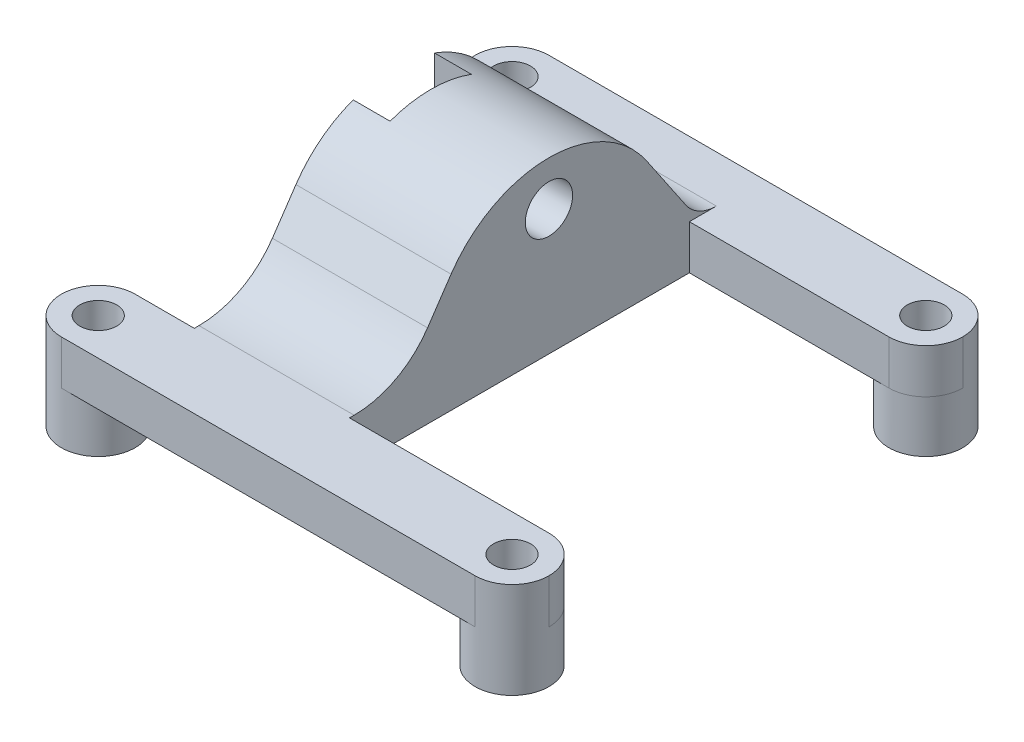
SolidWorks part; units mm, degrees
ref_plane "Plan de face" through (0, 0, 0) normal (0, 0, 1) x (1, 0, 0)
ref_plane "Plan de dessus" through (0, 0, 0) normal (0, 1, 0) x (1, 0, 0)
ref_plane "Plan de droite" through (0, 0, 0) normal (1, 0, 0) x (0, 0, -1)
sketch "Esquisse2" plane through (0, 0, 0) normal (0, 1, 0) x (1, 0, 0)
  line L0 (-16.5, 0) -> (16.5, 0) construction
  line L1 (-16.5, 16.5) -> (16.5, 16.5)
  line L2 (-16.5, 16.5) -> (-16.5, -16.5)
  line L3 (-16.5, -16.5) -> (16.5, -16.5)
  line L4 (16.5, 16.5) -> (16.5, -16.5)
  line L5 (-14, 0) -> (14, 0) construction
  line L6 (-14, 14) -> (14, 14) construction
  line L7 (-14, 14) -> (-14, -14) construction
  line L8 (-14, -14) -> (14, -14) construction
  line L9 (14, 14) -> (14, -14) construction
  circle A0 centre (-14, 14) radius 1.25
  circle A1 centre (14, 14) radius 1.25
  circle A2 centre (-14, -14) radius 1.25
  circle A3 centre (14, -14) radius 1.25
  dimension "D4" = 2.5
  dimension "D5" = 2.5
  dimension "D6" = 2.5
  dimension "D7" = 2.5
  dimension "D1" = 33
  dimension "D2" = 33
  dimension "D3" = 28
extrude "Boss.-Extru.1" add sketch "Esquisse2" along normal blind 3
fillet "Congé1" radius 2.5 4 edges at (-16.5, 1.5, -16.5) (16.5, 1.5, -16.5) (16.5, 1.5, 16.5) (-16.5, 1.5, 16.5)
sketch "Esquisse3" plane through (0, 0, 0) normal (0, -1, 0) x (1, 0, 0)
  circle A0 centre (-14, 14) radius 2.5
  arc A3 (-14, 16.5) -> (-16.5, 14) centre (-14, 14) ccw construction
  circle A4 centre (-14, 14) radius 1.25
  circle A5 centre (-14, 14) radius 1.25 construction
  circle A6 centre (14, 14) radius 2.5
  circle A7 centre (14, 14) radius 1.25
  circle A8 centre (14, 14) radius 1.25 construction
  arc A9 (16.5, 14) -> (14, 16.5) centre (14, 14) ccw construction
  circle A10 centre (14, -14) radius 2.5
  circle A11 centre (14, -14) radius 1.25
  circle A12 centre (14, -14) radius 1.25 construction
  arc A13 (14, -16.5) -> (16.5, -14) centre (14, -14) ccw construction
  circle A14 centre (-14, -14) radius 2.5
  arc A15 (-16.5, -14) -> (-14, -16.5) centre (-14, -14) ccw construction
  circle A16 centre (-14, -14) radius 1.25
  circle A17 centre (-14, -14) radius 1.25 construction
extrude "Boss.-Extru.2" add sketch "Esquisse3" along normal blind 3.5
sketch "Esquisse4" plane through (0, 0, 0) normal (1, 0, 0) x (0, 0, -1)
  line L0 (-11.5, -3.5) -> (-11.5, 3) construction
  line L1 (-14, 3) -> (14, 3) construction
  line L2 (2, 11.5) -> (2, -0.9111) construction
  line L4 (-4.6243, 7.9854) -> (-8, 3)
  line L5 (2, -0.9111) -> (2, -3.5) construction
  line L6 (-8, 3) -> (12, 3)
  line L7 (-11.5, -3.5) -> (2, -3.5) construction
  line L8 (8.6243, 7.9854) -> (12, 3)
  arc A1 (-4.6243, 7.9854) -> (8.6243, 7.9854) centre (2, 3.5) cw
  point P18 (0, 3)
  dimension "D1" = 15
  dimension "D2" = 7
  dimension "D3" = 8
  dimension "D4" = 2
extrude "Boss.-Extru.3" add sketch "Esquisse4" along normal up to surface and the other way up to surface up to face at (16.5, 1.5, 0) other way up to face at (-16.5, 1.5, 0)
sketch "Esquisse5" plane through (0, 0, 0) normal (0, 1, 0) x (1, 0, 0)
  line L0 (16.5, -14) -> (16.5, 14) construction
  line L1 (16.5, 11.5) -> (0.5, 11.5)
  line L2 (16.5, 11.5) -> (16.5, -11.5)
  line L3 (16.5, -11.5) -> (0.5, -11.5)
  line L4 (0.5, 11.5) -> (0.5, -11.5)
  line L5 (-16.5, 0) -> (16.5, 0) construction
  line L6 (-16.5, 14) -> (-16.5, -14) construction
  line L7 (0, -16.5) -> (0, 16.5) construction
  line L8 (-14, -16.5) -> (14, -16.5) construction
  line L9 (14, 16.5) -> (-14, 16.5) construction
  line L10 (-10, 11.5) -> (-10, -11.5)
  line L11 (-16.5, -11.5) -> (-10, -11.5)
  line L12 (-16.5, 11.5) -> (-16.5, -11.5)
  line L13 (-16.5, 11.5) -> (-10, 11.5)
  circle A0 centre (14, 14) radius 1.25 construction
  point P13 (16.5, 0)
  dimension "D1" = 2.5
  dimension "D2" = 0.5
  dimension "D3" = 10
extrude "Enlèv. mat.-Extru.1" cut sketch "Esquisse5" against normal through all both and the other way through all
sketch "Esquisse6" plane through (-10, 0, 0) normal (-1, 0, 0) x (0, 0, 1)
  line L0 (-2, 0) -> (-2, 11.5) construction
  line L2 (-2, 5.3246) -> (-4.75, 6.9123)
  line L3 (-4.75, 6.9123) -> (-4.75, 11.0125)
  line L4 (-2, 5.3246) -> (0.75, 6.9123)
  line L5 (0.75, 6.9123) -> (0.75, 11.0125)
  line L6 (-4.75, 6.9123) -> (0.75, 6.9123) construction
  line L7 (11.5, 0) -> (-11.5, 0) construction
  arc A0 (4.6243, 7.9854) -> (-8.6243, 7.9854) centre (-2, 3.5) ccw construction
  circle A1 centre (-2, 8.5) radius 2.75 construction
  arc A2 (-4.75, 11.0125) -> (0.75, 11.0125) centre (-2, 3.5) cw
  point P25 (-3.375, 6.1184)
  dimension "D1" = 5.5
  dimension "D2" = 8.5
extrude "Enlèv. mat.-Extru.2" cut sketch "Esquisse6" against normal blind 2.5
sketch "Esquisse7" plane through (0.5, 0, 0) normal (1, 0, 0) x (0, 0, -1)
  line L0 (2, 8.5) -> (2, 0) construction
  line L1 (11.5, 0) -> (-11.5, 0) construction
  circle A0 centre (2, 8.5) radius 1.6
  dimension "D2" = 3.2
  dimension "D1" = 8.5
  dimension "D3" = 2
extrude "Enlèv. mat.-Extru.3" cut sketch "Esquisse7" against normal through all
fillet "Congé2" radius 2.5 4 edges at (16.5, 1.8692, -11.5) (16.5, 1.5, 11.5) (-16.5, 1.5, 11.5) (-16.5, 1.8692, -11.5)
fillet "Congé3" radius 2.5 1 edges at (0, 3, -12)
fillet "Congé4" radius 6 1 edges at (-4.75, 3, 8)
sketch "Esquisse8" plane through (0.5, 0, 0) normal (1, 0, 0) x (0, 0, -1)
  line L0 (11.5, 0) -> (11.5, 3.7929) construction
  line L1 (16.5, 3) -> (11.5, 3)
  line L2 (16.5, 3) -> (16.5, 6)
  line L3 (16.5, 6) -> (11.5, 6)
  line L4 (11.5, 3) -> (11.5, 6)
  dimension "D1" = 3
extrude "Enlèv. mat.-Extru.4" cut sketch "Esquisse8" along normal through all
sketch "Esquisse9" plane through (-10, 0, 0) normal (-1, 0, 0) x (0, 0, 1)
  line L0 (-11.5, 0) -> (-11.5, 3.7929) construction
  line L1 (-16.5, 6) -> (-11.5, 6)
  line L2 (-16.5, 6) -> (-16.5, 3)
  line L3 (-16.5, 3) -> (-11.5, 3)
  line L4 (-11.5, 6) -> (-11.5, 3)
  dimension "D1" = 3
extrude "Enlèv. mat.-Extru.5" cut sketch "Esquisse9" along normal through all
